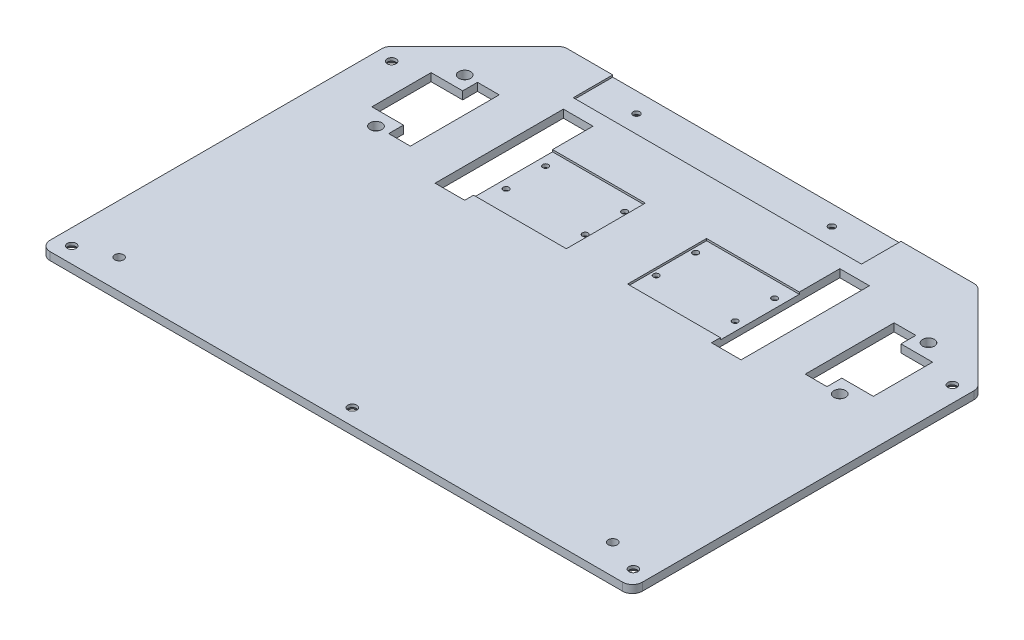
SolidWorks part; units mm, degrees
material "Acier non allié"
ref_plane "Front" through (0, 0, 0) normal (0, 0, 1) x (1, 0, 0)
ref_plane "Top" through (0, 0, 0) normal (0, 1, 0) x (1, 0, 0)
ref_plane "Right" through (0, 0, 0) normal (1, 0, 0) x (0, 0, -1)
sketch "Main scetch" plane through (0, 0, 0) normal (0, 1, 0) x (1, 0, 0)
  line L0 (-150, 0) -> (150, 0)
  line L1 (0, 0) -> (150, 0) construction
  line L2 (0, 0) -> (0, 220) construction
  line L3 (0, 220) -> (150, 220) construction
  line L4 (150, 0) -> (150, 220) construction
  line L5 (150, 0) -> (150, 175)
  line L6 (150, 175) -> (105, 220)
  line L10 (105, 220) -> (-105, 220)
  line L11 (-150, 0) -> (-150, 175)
  line L12 (-150, 175) -> (-105, 220)
  dimension "D1" = 150
  dimension "D2" = 220
  dimension "D3" = 45
  dimension "D4" = 45
extrude "Main extrusion" add sketch "Main scetch" along normal blind 4
fillet "Corner leave" radius 5 6 edges at (-150, 2, 0) (150, 2, -175) (105, 2, -220) (150, 2, 0) (-105, 2, -220) (-150, 2, -175)
sketch "Esquisse2" plane through (0, 4, 0) normal (0, 1, 0) x (1, 0, 0)
  line L0 (-145, 0) -> (145, 0) construction
  line L1 (150, 5) -> (150, 172.9289) construction
  line L2 (148.5355, 176.4645) -> (106.4645, 218.5355) construction
  line L3 (102.9289, 220) -> (-102.9289, 220) construction
  line L4 (-106.4645, 218.5355) -> (-148.5355, 176.4645) construction
  line L5 (-150, 172.9289) -> (-150, 5) construction
  line L6 (-145, 0) -> (145, 0) construction
  line L7 (150, 5) -> (150, 172.9289) construction
  line L8 (148.5355, 176.4645) -> (106.4645, 218.5355) construction
  line L9 (102.9289, 220) -> (-102.9289, 220) construction
  line L10 (-106.4645, 218.5355) -> (-148.5355, 176.4645) construction
  line L11 (-150, 172.9289) -> (-150, 5) construction
  line L12 (0, 0) -> (0, 238.9669) construction
  line L13 (0, 160) -> (165.6987, 160) construction
  line L14 (70, 230.4421) -> (70, 102.0601) construction
  line L15 (62.5, 192.5) -> (77.5, 192.5)
  line L16 (62.5, 192.5) -> (62.5, 127.5)
  line L17 (62.5, 127.5) -> (77.5, 127.5)
  line L18 (77.5, 192.5) -> (77.5, 127.5)
  line L19 (100, 137.5) -> (100, 182.5)
  line L20 (100, 182.5) -> (111, 182.5)
  line L22 (127, 175) -> (127, 145)
  line L23 (100, 137.5) -> (111, 137.5)
  line L35 (111, 182.5) -> (111, 175)
  line L36 (111, 175) -> (127, 175)
  line L37 (111, 137.5) -> (111, 145)
  line L38 (111, 145) -> (127, 145)
  line L39 (-111, 137.5) -> (-111, 145)
  line L40 (-100, 137.5) -> (-111, 137.5)
  line L41 (-100, 137.5) -> (-100, 182.5)
  line L42 (-100, 182.5) -> (-111, 182.5)
  line L43 (-111, 182.5) -> (-111, 175)
  line L44 (-111, 175) -> (-127, 175)
  line L45 (-127, 175) -> (-127, 145)
  line L46 (-111, 145) -> (-127, 145)
  line L47 (-62.5, 127.5) -> (-77.5, 127.5)
  line L48 (-77.5, 192.5) -> (-77.5, 127.5)
  line L49 (-62.5, 192.5) -> (-77.5, 192.5)
  line L50 (-62.5, 192.5) -> (-62.5, 127.5)
  circle A0 centre (117.47, 182.47) radius 3
  circle A1 centre (117.47, 137.53) radius 3
  circle A2 centre (-117.47, 137.53) radius 3
  circle A3 centre (-117.47, 182.47) radius 3
  point P28 (127, 160)
  point P29 (100, 160)
  dimension "D12" = 6
  dimension "D1" = 60
  dimension "D2" = 65
  dimension "D3" = 70
  dimension "D4" = 15
  dimension "D5" = 27
  dimension "D6" = 45
  dimension "D7" = 100
  dimension "D8" = 11
  dimension "D9" = 30
  dimension "D10" = 17.47
  dimension "D11" = 22.47
extrude "Enlèv. mat.-Extru.1" cut sketch "Esquisse2" against normal through all
sketch "Esquisse8" plane through (0, 4, 0) normal (0, 1, 0) x (1, 0, 0)
  line L0 (-150, 172.9289) -> (-150, 5) construction
  line L1 (-145, 0) -> (145, 0) construction
  line L3 (150, 5) -> (150, 172.9289) construction
  circle A0 centre (-125, 15) radius 1.5
  circle A1 centre (125, 15) radius 1.5
  dimension "D1" = 3
  dimension "D4" = 3
  dimension "D6" = 25
  dimension "D2" = 25
  dimension "D3" = 15
  dimension "D5" = 15
hole_wizard "Dégagement M41" positions "Esquisse16" profile "Esquisse17" hole size "M4" standard "ISO" end condition through all
sketch "Esquisse16" plane through (0, 4, 0) normal (0, 1, 0) x (1, 0, 0)
  point P0 (-125, 15)
  point P3 (125, 15)
sketch "Esquisse17" plane through (-125, 4, -15) normal (1, 0, 0) x (0, 0, 1)
  line L0 (0, 0) -> (0, 4)
  line L1 (0, 4) -> (2.25, 4)
  line L2 (2.25, 4) -> (2.25, 0)
  line L5 (2.25, 0) -> (0, 0)
  line L11 (0, -6.35) -> (0, 107.95) construction
  dimension "Diamètre du perçage jusqu'au prochain" = 4.5
  dimension "Profondeur du perçage jusqu'au prochain" = 4
sketch "Esquisse18" plane through (0, 4, 0) normal (0, 1, 0) x (1, 0, 0)
  line L0 (-150, 172.9289) -> (-150, 5) construction
  line L1 (-145, 0) -> (145, 0) construction
  line L3 (150, 5) -> (150, 172.9289) construction
  circle A0 centre (-142, 8) radius 1
  circle A1 centre (-142, 170) radius 1
  circle A4 centre (142, 170) radius 1
  circle A5 centre (142, 8) radius 1
  circle A6 centre (0, 8) radius 1.5
  dimension "D1" = 2
  dimension "D2" = 2
  dimension "D3" = 3
  dimension "D4" = 8
  dimension "D5" = 2
  dimension "D6" = 2
  dimension "D7" = 8
  dimension "D8" = 8
  dimension "D9" = 170
  dimension "D10" = 8
  dimension "D15" = 8
  dimension "D16" = 170
  dimension "D17" = 8
  dimension "D18" = 8
sketch "Esquisse23" plane through (0, 4, 0) normal (0, 1, 0) x (1, 0, 0)
  line L0 (-62.5, 127.5) -> (-62.5, 192.5) construction
  line L1 (-62.5, 172) -> (-15.5, 172)
  line L2 (-62.5, 172) -> (-62.5, 132)
  line L3 (-62.5, 132) -> (-15.5, 132)
  line L4 (-15.5, 172) -> (-15.5, 132)
  line L6 (-62.5, 160) -> (-12.8793, 160) construction
  point P9 (-62.5, 160)
  dimension "D1" = 40
  dimension "D2" = 47
  dimension "D3" = 12
extrude "Enlèv. mat.-Extru.2" cut sketch "Esquisse23" against normal blind 1
sketch "Esquisse24" plane through (0, 3, 0) normal (0, 1, 0) x (1, 0, 0)
  line L0 (-58, 212.7511) -> (-58, 75.2489) construction
  line L1 (-62.5, 172) -> (-62.5, 132) construction
  line L2 (-15.5, 172) -> (-62.5, 172) construction
  line L3 (-18, 126.9657) -> (-18, 195.1017) construction
  line L4 (-58, 164) -> (-9.2469, 164) construction
  line L5 (-58, 144) -> (-13.1999, 144) construction
  circle A0 centre (-58, 164) radius 1
  circle A1 centre (-58, 144) radius 1
  circle A2 centre (-18, 164) radius 1
  circle A3 centre (-18, 144) radius 1
  dimension "D1" = 2
  dimension "D2" = 2
  dimension "D7" = 2
  dimension "D8" = 2
  dimension "D3" = 20
  dimension "D4" = 4.5
  dimension "D5" = 8
  dimension "D6" = 40
extrude "Enlèv. mat.-Extru.3" cut sketch "Esquisse24" against normal through all
hole_wizard "Fraisage pour vis à tête fraisée M2.51" positions "Esquisse27" profile "Esquisse28" countersink size "M2.5" standard "ISO" end condition through all
sketch "Esquisse27" plane through (0, 0, 0) normal (0, -1, 0) x (-1, 0, 0)
  point P0 (18, 164)
  point P3 (58, 164)
  point P6 (58, 144)
  point P9 (18, 144)
sketch "Esquisse28" plane through (-18, 0, -164) normal (1, 0, 0) x (0, 0, -1)
  line L0 (0, 0) -> (0, 4)
  line L1 (0, 4) -> (1.45, 4)
  line L2 (1.45, 4) -> (1.45, 1.3)
  line L3 (1.45, 1.3) -> (2.75, 0)
  line L5 (2.75, 0) -> (0, 0)
  line L6 (-1.45, 1.3) -> (-2.75, 0) construction
  line L11 (0, -6.35) -> (0, 107.95) construction
  dimension "Diamètre du perçage jusqu'au prochain" = 2.9
  dimension "Profondeur du perçage jusqu'au prochain" = 4
  dimension "Diamètre du fraisage entrant" = 5.5
  dimension "Angle du fraisage entrant" = 90
mirror "Symétrie1" about plane through (0, 0, 0) normal (1, 0, 0) of "Enlèv. mat.-Extru.3", "Fraisage pour vis à tête fraisée M2.51", "Enlèv. mat.-Extru.2"
hole_wizard "Fraisage pour vis à tête fraisée M41" positions "Esquisse30" profile "Esquisse31" countersink size "M4" standard "ISO" end condition through all
sketch "Esquisse30" plane through (0, 0, 0) normal (0, -1, 0) x (-1, 0, 0)
  point P0 (-142.0349, 8.4348)
  point P2 (0, 8.1016)
  point P4 (0, 8.1016)
  point P6 (142, 8)
  point P9 (142, 170)
  point P12 (-142, 170)
sketch "Esquisse31" plane through (142.0349, 0, -8.4348) normal (1, 0, 0) x (0, 0, -1)
  line L0 (0, 0) -> (0, 4)
  line L1 (0, 4) -> (2.25, 4)
  line L2 (2.25, 4) -> (2.25, 2.45)
  line L3 (2.25, 2.45) -> (4.7, 0)
  line L5 (4.7, 0) -> (0, 0)
  line L6 (-2.25, 2.45) -> (-4.7, 0) construction
  line L11 (0, -6.35) -> (0, 107.95) construction
  dimension "Diamètre du perçage jusqu'au prochain" = 4.5
  dimension "Profondeur du perçage jusqu'au prochain" = 4
  dimension "Diamètre du fraisage entrant" = 9.4
  dimension "Angle du fraisage entrant" = 90
sketch "Esquisse32" plane through (0, 4, 0) normal (0, 1, 0) x (1, 0, 0)
  line L0 (102.9289, 220) -> (-102.9289, 220) construction
  line L1 (-80, 220) -> (66, 220)
  line L2 (-80, 220) -> (-80, 200)
  line L3 (-80, 200) -> (66, 200)
  line L4 (66, 220) -> (66, 200)
  line L5 (150, 5) -> (150, 172.9289) construction
  dimension "D1" = 84
  dimension "D2" = 146
  dimension "D3" = 20
extrude "Enlèv. mat.-Extru.4" cut sketch "Esquisse32" against normal blind 1
sketch "Esquisse33" plane through (0, 0, 0) normal (0, -1, 0) x (1, 0, 0)
  line L4 (-80, -200) -> (-80, -220)
  line L5 (66, -200) -> (-80, -200)
  line L6 (66, -220) -> (66, -200)
  line L7 (-80, -220) -> (66, -220)
  line L8 (-80, -200) -> (-80, -220) construction
  line L9 (66, -200) -> (-80, -200) construction
  line L10 (66, -220) -> (66, -200) construction
  line L11 (-80, -220) -> (66, -220) construction
  circle A0 centre (-58, -210) radius 1
  circle A1 centre (41, -210) radius 1
  dimension "D4" = 2
  dimension "D7" = 2
  dimension "D2" = 22
  dimension "D3" = 10
  dimension "D5" = 25
  dimension "D6" = 10
  dimension "D1" = 0
extrude "Enlèv. mat.-Extru.5" cut sketch "Esquisse33" against normal through all
hole_wizard "Fraisage pour vis à tête fraisée M31" positions "Esquisse34" profile "Esquisse35" countersink size "M3" standard "ISO" end condition through all
sketch "Esquisse34" plane through (0, 0, 0) normal (0, -1, 0) x (-1, 0, 0)
  point P0 (58, 210)
  point P3 (-41, 210)
sketch "Esquisse35" plane through (-58, 0, -210) normal (1, 0, 0) x (0, 0, -1)
  line L0 (0, 0) -> (0, 4)
  line L1 (0, 4) -> (1.7, 4)
  line L2 (1.7, 4) -> (1.7, 1.45)
  line L3 (1.7, 1.45) -> (3.15, 0)
  line L5 (3.15, 0) -> (0, 0)
  line L6 (-1.7, 1.45) -> (-3.15, 0) construction
  line L11 (0, -6.35) -> (0, 107.95) construction
  dimension "Diamètre du perçage jusqu'au prochain" = 3.4
  dimension "Profondeur du perçage jusqu'au prochain" = 4
  dimension "Diamètre du fraisage entrant" = 6.3
  dimension "Angle du fraisage entrant" = 90
equation "\"WIDTH\"= 300mm'Total width of the robot"
equation "\"LENGTH\"= 220mm'Total length of the robot"
equation "\"D1@Main scetch\" = \"WIDTH\" / 2"
equation "\"D2@Main scetch\" = \"LENGTH\""
equation "\"CUT_DEPTH\"= 45mm'Depth of the cut on the edges of the plate"
equation "\"D3@Main scetch\" = \"CUT_DEPTH\""
equation "\"D4@Main scetch\" = \"CUT_DEPTH\""
equation "\"Plate_th\"= 3mm'Thickness of the plate"
equation "\"D1\"= \"Plate_th\""
